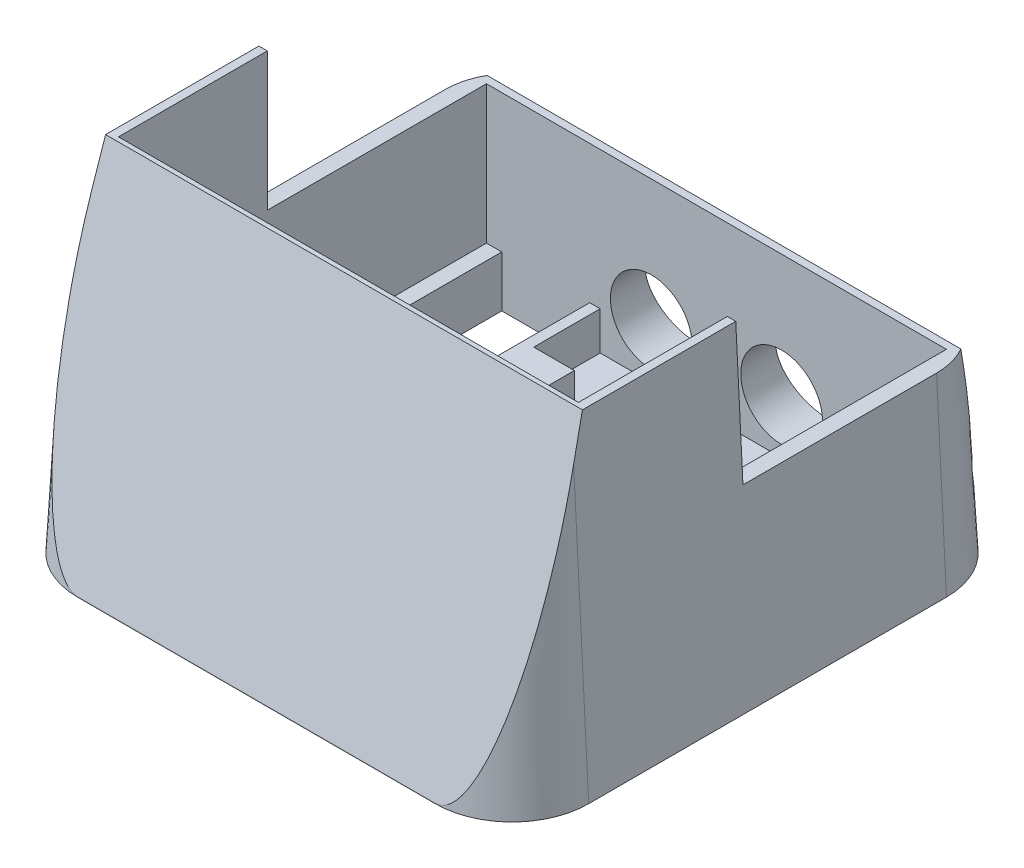
SolidWorks part; units mm, degrees
ref_plane "Front Plane" through (0, 0, 0) normal (0, 0, 1) x (1, 0, 0)
ref_plane "Top Plane" through (0, 0, 0) normal (0, 1, 0) x (1, 0, 0)
ref_plane "Right Plane" through (0, 0, 0) normal (1, 0, 0) x (0, 0, -1)
sketch "Sketch1" plane through (0, 0, 0) normal (0, 1, 0) x (1, 0, 0)
  line L0 (-35, 50) -> (35, 50)
  line L5 (50, 35) -> (50, -35)
  line L6 (-50, 35) -> (-50, -35)
  line L7 (-35, -50) -> (35, -50)
  arc A0 (35, -50) -> (50, -35) centre (35, -35) ccw
  arc A1 (-50, -35) -> (-35, -50) centre (-35, -35) ccw
  arc A2 (-50, 35) -> (-35, 50) centre (-35, 35) cw
  arc A3 (35, 50) -> (50, 35) centre (35, 35) cw
  point P14 (0, -50)
  point P19 (-50, 0)
  dimension "D3" = 15
  dimension "D4" = 15
  dimension "D5" = 15
  dimension "D6" = 15
  dimension "D1" = 100
  dimension "D2" = 100
extrude "Boss-Extrude1" add sketch "Sketch1" along normal blind 10
sketch "Sketch2" plane through (0, 10, 0) normal (0, 1, 0) x (1, 0, 0)
  line L0 (-50, 35) -> (-50, -35) construction
  line L1 (-42, 40) -> (-24.8, 40)
  line L2 (-42, 40) -> (-42, -3)
  line L3 (-42, -3) -> (-24.8, -3)
  line L4 (-24.8, 40) -> (-24.8, -3)
  line L5 (-42, 40) -> (-24.8, -3) construction
  line L6 (-42, -3) -> (-24.8, 40) construction
  line L7 (24.8, 40) -> (42, 40)
  line L8 (24.8, 40) -> (24.8, -3)
  line L9 (24.8, -3) -> (42, -3)
  line L10 (42, 40) -> (42, -3)
  line L11 (24.8, 40) -> (42, -3) construction
  line L12 (24.8, -3) -> (42, 40) construction
  line L13 (50, -35) -> (50, 35) construction
  line L15 (35, 50) -> (-35, 50) construction
  point P0 (-33.4, 18.5)
  point P5 (33.4, 18.5)
  dimension "D1" = 8
  dimension "D2" = 8
  dimension "D3" = 17.2
  dimension "D4" = 17.2
  dimension "D5" = 43
  dimension "D6" = 43
  dimension "D7" = 10
  dimension "D8" = 10
extrude "Cut-Extrude1" cut sketch "Sketch2" against normal through all
sketch "Sketch3" plane through (0, 10, 0) normal (0, 1, 0) x (1, 0, 0)
  line L1 (-40, -8) -> (40, -8)
  line L2 (-40, -8) -> (-40, -32)
  line L3 (-40, -32) -> (40, -32)
  line L4 (40, -8) -> (40, -32)
  line L5 (-40, -8) -> (40, -32) construction
  line L6 (-40, -32) -> (40, -8) construction
  line L7 (-45, -3) -> (45, -3)
  line L8 (-45, -3) -> (-45, -37)
  line L9 (-45, -37) -> (45, -37)
  line L10 (45, -3) -> (45, -37)
  line L11 (-45, -3) -> (45, -37) construction
  line L12 (-45, -37) -> (45, -3) construction
  line L13 (-35, -50) -> (35, -50) construction
  line L14 (-42, -3) -> (-24.8, -3) construction
  point P0 (0, -20)
  point P5 (0, -20)
  point P18 (0, -50)
  dimension "D1" = 24
  dimension "D2" = 80
  dimension "D3" = 34
  dimension "D4" = 90
extrude "Boss-Extrude3" add sketch "Sketch3" along normal blind 15
sketch "Sketch4" plane through (0, 10, 0) normal (0, 1, 0) x (1, 0, 0)
  line L0 (24.8, 40) -> (24.8, -3) construction
  line L3 (-24.8, 12.5) -> (24.8, 12.5)
  line L5 (-24.8, 24.5) -> (24.8, 24.5)
  line L6 (-24.8, 29.5) -> (24.8, 29.5)
  line L11 (-24.8, 7.5) -> (24.8, 7.5)
  line L12 (-24.8, 29.5) -> (-24.8, 24.5)
  line L13 (-24.8, -3) -> (-24.8, 40) construction
  line L14 (-24.8, 12.5) -> (-24.8, 7.5)
  line L15 (24.8, 12.5) -> (24.8, 7.5)
  line L16 (24.8, 29.5) -> (24.8, 24.5)
  point P4 (-24.8, 18.5)
  dimension "D1" = 5
  dimension "D2" = 12
  dimension "D3" = 5
  dimension "D4" = 6
extrude "Boss-Extrude4" add sketch "Sketch4" along normal blind 10
sketch "Sketch5" plane through (0, 20, 0) normal (0, 1, 0) x (1, 0, 0)
  line L0 (-24.8, 7.5) -> (24.8, 7.5) construction
  line L1 (-24.8, 29.5) -> (-9.8, 29.5)
  line L2 (-24.8, 29.5) -> (-24.8, 7.5)
  line L3 (-24.8, 7.5) -> (-9.8, 7.5)
  line L4 (-9.8, 29.5) -> (-9.8, 7.5)
  line L6 (24.8, 29.5) -> (9.8, 29.5)
  line L7 (24.8, 29.5) -> (24.8, 7.5)
  line L8 (24.8, 7.5) -> (9.8, 7.5)
  line L9 (9.8, 29.5) -> (9.8, 7.5)
  dimension "D1" = 15
  dimension "D2" = 15
extrude "Boss-Extrude5" add sketch "Sketch5" along normal blind 5
sketch "Sketch6" plane through (0, 10, 0) normal (0, 1, 0) x (1, 0, 0)
  line L1 (-45, -37) -> (45, -37)
  line L2 (-45, -37) -> (-45, 40)
  line L3 (-45, 40) -> (45, 40)
  line L4 (45, -37) -> (45, 40)
  line L5 (45, -37) -> (45, -3) construction
  line L6 (-24.8, 40) -> (-42, 40) construction
  line L7 (-50, 35) -> (-50, -35) construction
  line L8 (-35, -50) -> (35, -50) construction
  line L9 (50, -35) -> (50, 35) construction
  line L10 (35, 50) -> (-35, 50) construction
  line L11 (-50, 35) -> (-50, -35)
  line L12 (-35, -50) -> (35, -50)
  line L13 (50, -35) -> (50, 35)
  line L14 (35, 50) -> (-35, 50)
  arc A0 (-50, -35) -> (-35, -50) centre (-35, -35) ccw construction
  arc A1 (35, -50) -> (50, -35) centre (35, -35) ccw construction
  arc A2 (50, 35) -> (35, 50) centre (35, 35) ccw construction
  arc A3 (-35, 50) -> (-50, 35) centre (-35, 35) ccw construction
  arc A4 (-50, -35) -> (-35, -50) centre (-35, -35) ccw
  arc A5 (35, -50) -> (50, -35) centre (35, -35) ccw
  arc A6 (50, 35) -> (35, 50) centre (35, 35) ccw
  arc A7 (-35, 50) -> (-50, 35) centre (-35, 35) ccw
extrude "Boss-Extrude6" add sketch "Sketch6" along normal up to surface (15 mm away) up to face at (0, 25, 20)
sketch "Sketch9" plane through (0, 25, 0) normal (0, 1, 0) x (1, 0, 0)
  line L22 (-50, 35) -> (-50, -35) construction
  line L23 (-35, -50) -> (35, -50) construction
  line L24 (50, -35) -> (50, 35) construction
  line L25 (35, 50) -> (-35, 50) construction
  line L26 (-45, 35) -> (-45, -35)
  line L27 (-35, -45) -> (35, -45)
  line L28 (45, -35) -> (45, 35)
  line L29 (35, 45) -> (-35, 45)
  line L30 (-45, 35) -> (-45, -32)
  line L32 (45, -32) -> (45, 35)
  line L34 (-50, 35) -> (-50, -35)
  line L35 (-35, -50) -> (35, -50)
  line L36 (50, -35) -> (50, 35)
  line L37 (35, 50) -> (-35, 50)
  line L38 (45, -32) -> (-45, -32)
  line L39 (-40, -32) -> (40, -32) construction
  line L40 (43.6603, 40) -> (-43.6603, 40)
  line L41 (45, 40) -> (-45, 40) construction
  arc A23 (-50, -35) -> (-35, -50) centre (-35, -35) ccw construction
  arc A24 (35, -50) -> (50, -35) centre (35, -35) ccw construction
  arc A25 (50, 35) -> (35, 50) centre (35, 35) ccw construction
  arc A26 (-35, 50) -> (-50, 35) centre (-35, 35) ccw construction
  arc A27 (-45, -35) -> (-35, -45) centre (-35, -35) ccw
  arc A28 (35, -45) -> (45, -35) centre (35, -35) ccw
  arc A29 (45, 35) -> (35, 45) centre (35, 35) ccw
  arc A30 (-35, 45) -> (-45, 35) centre (-35, 35) ccw
  arc A33 (45, 35) -> (43.6603, 40) centre (35, 35) ccw
  arc A34 (-43.6603, 40) -> (-45, 35) centre (-35, 35) ccw
  arc A35 (-50, -35) -> (-35, -50) centre (-35, -35) ccw
  arc A36 (35, -50) -> (50, -35) centre (35, -35) ccw
  arc A37 (50, 35) -> (35, 50) centre (35, 35) ccw
  arc A38 (-35, 50) -> (-50, 35) centre (-35, 35) ccw
  dimension "D1" = 5
extrude "Boss-Extrude8" add sketch "Sketch9" along normal blind 39
chamfer "Chamfer1" distance 64 angle 3 8 edges at (0, 64, 50) (45.6066, 64, 45.6066) (-45.6066, 64, 45.6066) (50, 64, 0) (-50, 64, 0) (45.6066, 64, -45.6066) (-45.6066, 64, -45.6066) (0, 64, -50) first distance on face at (0, 32, 50) first distance on face at (44.0533, 32, 44.0533) first distance on face at (-44.0533, 32, 44.0533) first distance on face at (50, 32, 0) first distance on face at (-50, 32, 0) first distance on face at (44.0533, 32, -44.0533) first distance on face at (-44.0533, 32, -44.0533) first distance on face at (0, 32, -50)
chamfer "Chamfer2" distance 64 angle 10 1 edges at (0, 64, -46.6459) tangent propagation no first distance on face at (0, 32, -48.323)
chamfer "Chamfer3" distance 64 angle 12 1 edges at (0, 64, 46.6459) tangent propagation no first distance on face at (0, 32, 48.323)
sketch "Sketch10" plane through (0, 1.3075, 0) normal (-1, 0, 0) x (0, 0, 1)
  line L0 (-35, 62.6925) -> (32.8702, 62.6925) construction
  line L1 (2.8702, 62.6925) -> (-47.1298, 62.6925)
  line L2 (2.8702, 62.6925) -> (2.8702, 35.6925)
  line L3 (2.8702, 35.6925) -> (-47.1298, 35.6925)
  line L4 (-47.1298, 62.6925) -> (-47.1298, 35.6925)
  dimension "D1" = 50
  dimension "D2" = 27
  dimension "D3" = 30
extrude "Cut-Extrude3" cut sketch "Sketch10" against normal through all and the other way through all
sketch "Sketch11" plane through (0, 10, 0) normal (0, 1, 0) x (1, 0, 0)
  line L0 (24.8, 29.5) -> (-24.8, 29.5) construction
  line L1 (-22.75, 29.5) -> (22.75, 29.5)
  line L2 (-22.75, 29.5) -> (-22.75, 40)
  line L3 (-22.75, 40) -> (22.75, 40)
  line L4 (22.75, 29.5) -> (22.75, 40)
  line L5 (43.6603, 40) -> (-43.6603, 40) construction
  line L9 (24.8, 40) -> (-24.8, 40) construction
  point P10 (0, 40)
  point P11 (0, 29.5)
  dimension "D1" = 45.5
extrude "Cut-Extrude4" cut sketch "Sketch11" against normal blind 7.5
sketch "Sketch14" plane through (0, 10, 0) normal (0, 1, 0) x (1, 0, 0)
  line L0 (-24.8, 29.5) -> (-22.75, 29.5) construction
  line L1 (-22.75, 29.5) -> (-22.75, 40) construction
  line L2 (-22.75, 40) -> (-24.8, 40) construction
  line L3 (-24.8, 40) -> (-24.8, 29.5) construction
  line L4 (24.8, 40) -> (22.75, 40) construction
  line L5 (22.75, 40) -> (22.75, 29.5) construction
  line L6 (22.75, 29.5) -> (24.8, 29.5) construction
  line L7 (24.8, 29.5) -> (24.8, 40) construction
  line L8 (-24.8, 29.5) -> (-22.75, 29.5)
  line L9 (-22.75, 29.5) -> (-22.75, 40)
  line L10 (-22.75, 40) -> (-24.8, 40)
  line L11 (-24.8, 40) -> (-24.8, 29.5)
  line L12 (24.8, 40) -> (22.75, 40)
  line L13 (22.75, 40) -> (22.75, 29.5)
  line L14 (22.75, 29.5) -> (24.8, 29.5)
  line L15 (24.8, 29.5) -> (24.8, 40)
extrude "Boss-Extrude9" add sketch "Sketch14" along normal up to surface (15 mm away) up to face at (-17.3, 25, -18.5)
sketch "Sketch15" plane through (0, 0, -40) normal (0, 0, 1) x (1, 0, 0)
  line L0 (22.75, 2.5) -> (-22.75, 2.5) construction
  line L1 (12.75, 12.75) -> (-12.75, 12.75) construction
  line L2 (0, -35.2) -> (0, 35.2) construction
  circle A0 centre (-12.75, 12.75) radius 8
  circle A1 centre (12.75, 12.75) radius 8
  point P9 (0, 12.75)
  dimension "D3" = 16
  dimension "D4" = 16
  dimension "D1" = 10.25
  dimension "D2" = 10.25
  dimension "D5" = 25.5
extrude "Cut-Extrude5" cut sketch "Sketch15" against normal through all
sketch "Sketch17" plane through (0, 0, -29.5) normal (0, 0, -1) x (-1, 0, 0)
  line L8 (-9.8, 25) -> (-22.75, 25)
  line L9 (-22.75, 25) -> (-22.75, 2.5)
  line L10 (-22.75, 2.5) -> (22.75, 2.5)
  line L11 (22.75, 2.5) -> (22.75, 25)
  line L12 (22.75, 25) -> (9.8, 25)
  line L13 (9.8, 25) -> (9.8, 20)
  line L14 (9.8, 20) -> (-9.8, 20)
  line L15 (-9.8, 20) -> (-9.8, 25)
  line L16 (-9.8, 25) -> (-22.75, 25)
  line L17 (-22.75, 25) -> (-22.75, 2.5)
  line L18 (-22.75, 2.5) -> (22.75, 2.5)
  line L19 (22.75, 2.5) -> (22.75, 25)
  line L20 (22.75, 25) -> (9.8, 25)
  line L21 (9.8, 25) -> (9.8, 20)
  line L22 (9.8, 20) -> (-9.8, 20)
  line L23 (-9.8, 20) -> (-9.8, 25)
  dimension "D1" = 0
extrude "Cut-Extrude6" cut sketch "Sketch17" against normal blind 2.5
sketch "Sketch18" plane through (0, 0, 0) normal (0, -1, 0) x (1, 0, 0)
  line L1 (-14.8, -27) -> (14.8, -27)
  line L2 (-14.8, -27) -> (-14.8, 18)
  line L3 (-14.8, 18) -> (14.8, 18)
  line L4 (14.8, -27) -> (14.8, 18)
  line L5 (-24.8, 3) -> (-24.8, -40) construction
  line L6 (24.8, -40) -> (24.8, 3) construction
  line L8 (22.75, -27) -> (-22.75, -27) construction
  line L9 (24.8, 3) -> (42, 3) construction
  dimension "D1" = 10
  dimension "D2" = 10
  dimension "D3" = 15
extrude "Cut-Extrude7" cut sketch "Sketch18" against normal up to surface (10 mm away) up to face at (0, 10, -18.5)
sketch "Sketch20" plane through (0, 25, 0) normal (0, -1, 0) x (1, 0, 0)
  line L0 (-45, -35) -> (-45, -40) construction
  line L1 (-45, -40) -> (-43.6603, -40) construction
  line L2 (45, -40) -> (45, -35) construction
  line L3 (43.6603, -40) -> (45, -40) construction
  line L4 (-45, -35) -> (-45, -40)
  line L5 (-45, -40) -> (-43.6603, -40)
  line L6 (45, -40) -> (45, -35)
  line L7 (43.6603, -40) -> (45, -40)
  arc A0 (-45, -35) -> (-43.6603, -40) centre (-35, -35) ccw construction
  arc A1 (43.6603, -40) -> (45, -35) centre (35, -35) ccw construction
  arc A2 (-45, -35) -> (-43.6603, -40) centre (-35, -35) ccw
  arc A3 (43.6603, -40) -> (45, -35) centre (35, -35) ccw
extrude "Cut-Extrude8" cut sketch "Sketch20" against normal blind 15
sketch "Sketch21" plane through (0, 0, 0) normal (0, -1, 0) x (1, 0, 0)
  line L0 (-14.8, 18) -> (-14.8, -27) construction
  line L1 (-14.8, 18) -> (14.8, 18)
  line L2 (-14.8, 18) -> (-14.8, -17)
  line L3 (-14.8, -17) -> (14.8, -17)
  line L4 (14.8, 18) -> (14.8, -17)
  line L5 (14.8, -27) -> (14.8, 18) construction
  line L7 (-14.8, -27) -> (14.8, -27) construction
  line L8 (14.8, 18) -> (-14.8, 18) construction
  dimension "D2" = 10
extrude "Boss-Extrude10" add sketch "Sketch21" against normal blind 2.5
sketch "Sketch22" plane through (0, 64, 0) normal (0, 1, 0) x (1, 0, 0)
  line L6 (-45, 40) -> (-45, -32)
  line L12 (-45, 40) -> (45, 40)
  line L13 (45, 40) -> (45, -32)
  line L14 (45, -32) -> (-45, -32)
extrude "Cut-Extrude9" cut sketch "Sketch22" against normal up to surface (54 mm away) up to face at (-19.8, 10, -2.25)
